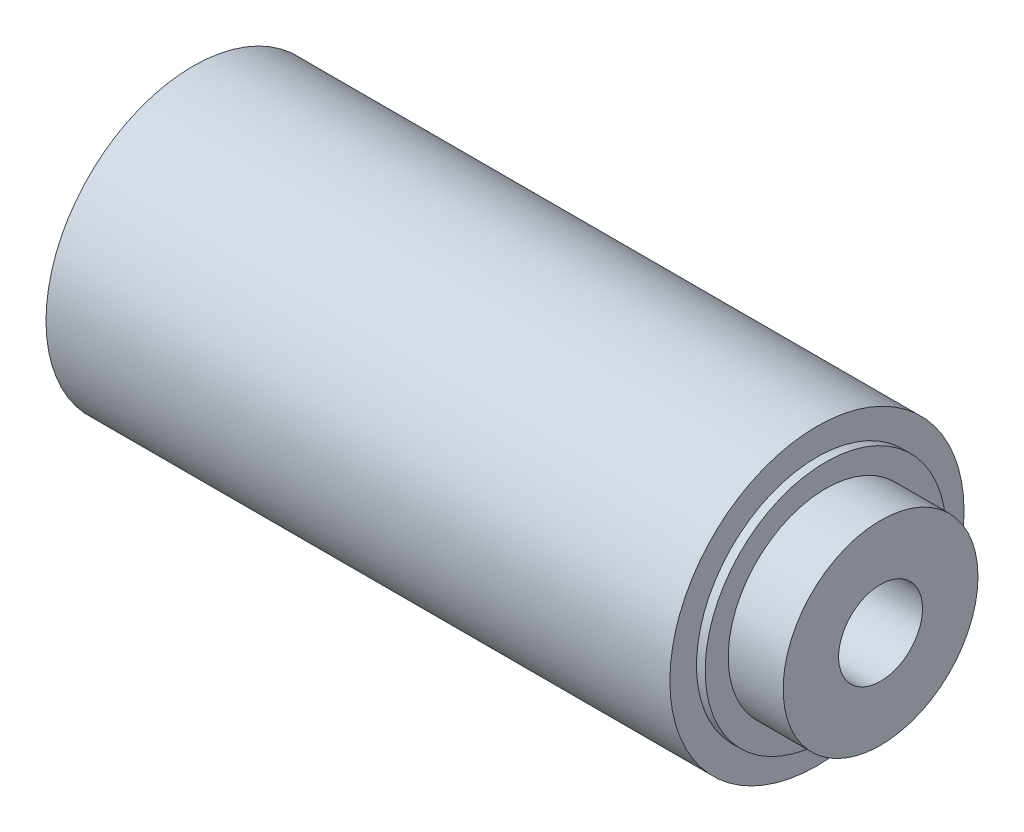
SolidWorks part; units mm, degrees
material "Water"
ref_plane "Front Plane" through (0, 0, 0) normal (0, 0, 1) x (1, 0, 0)
ref_plane "Top Plane" through (0, 0, 0) normal (0, 1, 0) x (1, 0, 0)
ref_plane "Right Plane" through (0, 0, 0) normal (1, 0, 0) x (0, 0, -1)
sketch "Sketch1" plane through (0, 0, 0) normal (1, 0, 0) x (0, 0, -1)
  circle A0 centre (0, 0) radius 54.345
  dimension "D1" = 108.69
extrude "Boss-Extrude1" add sketch "Sketch1" along normal blind 254
sketch "Sketch2" plane through (0, 0, 0) normal (1, 0, 0) x (0, 0, -1)
  line L1 (-28.194, 28.194) -> (28.194, 28.194)
  line L2 (-28.194, 28.194) -> (-28.194, -28.194)
  line L3 (-28.194, -28.194) -> (28.194, -28.194)
  line L4 (28.194, 28.194) -> (28.194, -28.194)
  line L5 (-28.194, 28.194) -> (28.194, -28.194) construction
  line L6 (-28.194, -28.194) -> (28.194, 28.194) construction
  circle A0 centre (-28.194, 28.194) radius 7.5
  circle A1 centre (28.194, 28.194) radius 7.5
  circle A2 centre (28.194, -28.194) radius 7.5
  circle A3 centre (-28.194, -28.194) radius 7.5
  point P0 (0, 0)
  point P16 (0, 0)
  dimension "D3" = 15
  dimension "D1" = 56.388
  dimension "D2" = 56.388
  dimension "D4" = 4
extrude "Cut-Extrude1" cut sketch "Sketch2" along normal blind 100 contours A3 L3 A2 L4 A1 L1 A0 L2 region at (0, 0, 0)
sketch "Sketch3" plane through (254, 0, 0) normal (1, 0, 0) x (0, 0, -1)
  circle A0 centre (0, 0) radius 44.5
  circle A1 centre (0, 0) radius 15.5
  circle A2 centre (0, 0) radius 7
  circle A3 centre (0, 0) radius 36
  circle M2 centre (0, 0) radius 54.345
  dimension "D1" = 89
  dimension "D2" = 72
  dimension "D3" = 31
  dimension "D4" = 14
extrude "Cut-Extrude2" cut sketch "Sketch3" against normal blind 139 contours A2 region at (254, 0, 0)
extrude "Cut-Extrude3" cut sketch "Sketch3<4>" against normal blind 65 contours A1 A2 region at (254, 0, 15.0616)
sketch "Sketch3<4>" plane through (254, 0, 0) normal (1, 0, 0) x (0, 0, -1) same geometry as "Sketch3"
extrude "Cut-Extrude4" cut sketch "Sketch3<6>" against normal blind 23.5 contours A0 M2 region at (254, 0, 52.8079)
sketch "Sketch3<6>" plane through (254, 0, 0) normal (1, 0, 0) x (0, 0, -1) same geometry as "Sketch3"
extrude "Cut-Extrude5" cut sketch "Sketch3<7>" against normal blind 20.3 contours A0 A3 region at (254, 0, 43.2413)
sketch "Sketch3<7>" plane through (254, 0, 0) normal (1, 0, 0) x (0, 0, -1) same geometry as "Sketch3"
chamfer "Chamfer1" distance 10 angle 45 1 edges at (189, 0, -15.5)
